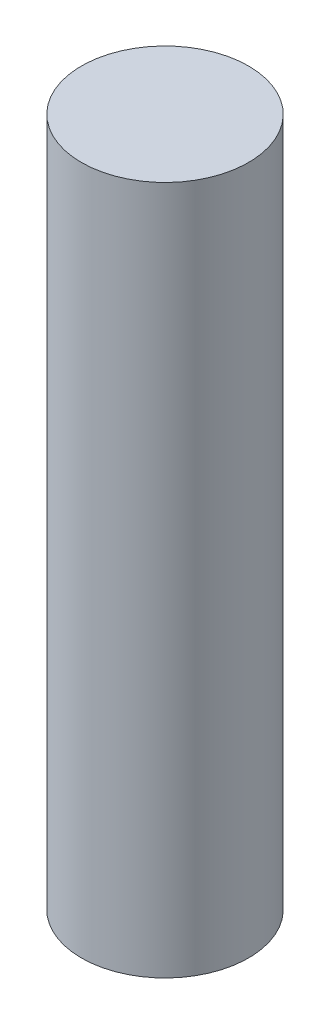
SolidWorks part; units mm, degrees
ref_plane "Front Plane" through (0, 0, 0) normal (0, 0, 1) x (1, 0, 0)
ref_plane "Top Plane" through (0, 0, 0) normal (0, 1, 0) x (1, 0, 0)
ref_plane "Right Plane" through (0, 0, 0) normal (1, 0, 0) x (0, 0, -1)
sketch "Sketch1" plane through (0, 0, 0) normal (0, 1, 0) x (1, 0, 0)
  circle A0 centre (0, 0) radius 2.9
  dimension "D1" = 5.8
extrude "Boss-Extrude1" add sketch "Sketch1" along normal blind 23.9
